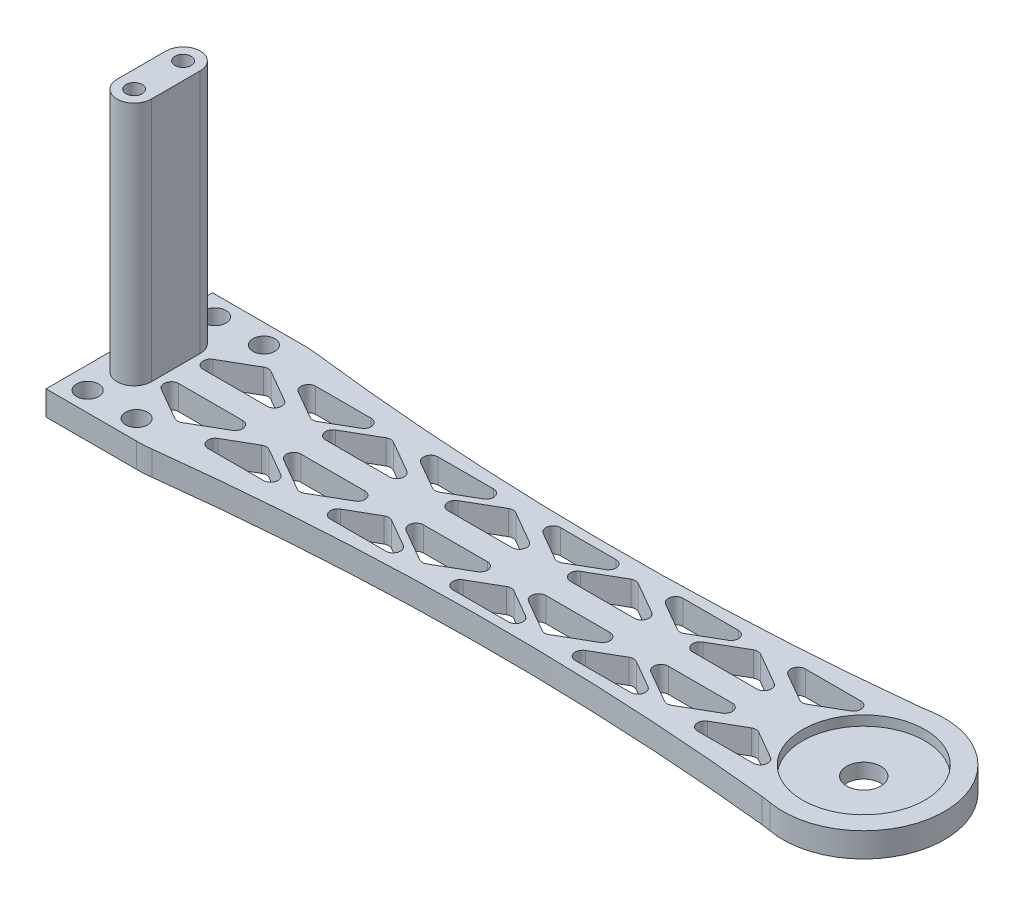
SolidWorks part; units mm, degrees
ref_plane "前视基准面" through (0, 0, 0) normal (0, 0, 1) x (1, 0, 0)
ref_plane "上视基准面" through (0, 0, 0) normal (0, 1, 0) x (1, 0, 0)
ref_plane "右视基准面" through (0, 0, 0) normal (1, 0, 0) x (0, 0, -1)
sketch "草图1" plane through (0, 0, 0) normal (0, 1, 0) x (1, 0, 0)
  line L0 (20, 17) -> (0, 17)
  line L1 (0, -28.047) -> (0, 28.047) construction
  line L2 (0, 17) -> (0, -17)
  line L3 (0, -17) -> (20, -17)
  line L5 (-45.4731, 0) -> (45.4731, 0) construction
  arc A0 (20, 17) -> (146.3579, 16.093) centre (87.1005, 562.8915) ccw
  arc A1 (146.3579, -16.093) -> (146.3579, 16.093) centre (150, 0) ccw
  arc A2 (20, -17) -> (146.3579, -16.093) centre (87.1005, -562.8915) cw
  dimension "D4" = 550
  dimension "D5" = 33
  dimension "D1" = 34
  dimension "D3" = 20
  dimension "D6" = 150
extrude "凸台-拉伸1" add sketch "草图1" along normal mid plane 5 contours A0 A1 A2 L3 L2 L0
sketch "草图2" plane through (0, 2.5, 0) normal (0, 1, 0) x (1, 0, 0)
  circle A0 centre (150, 0) radius 12.5
  dimension "D1" = 25
extrude "切除-拉伸1" cut sketch "草图2" against normal blind 2
sketch "草图3" plane through (0, 0.5, 0) normal (0, 1, 0) x (1, 0, 0)
  circle A0 centre (150, 0) radius 3.5
  dimension "D1" = 7
extrude "切除-拉伸2" cut sketch "草图3" against normal through all
sketch "草图4" plane through (0, 2.5, 0) normal (0, 1, 0) x (1, 0, 0)
  line L0 (12.5981, 2.5) -> (25.6506, 2.5)
  line L1 (26.4006, 5.299) -> (19.8744, 9.067)
  line L2 (18.3744, 9.067) -> (11.8481, 5.299)
  line L3 (-45.4731, 0) -> (45.4731, 0) construction
  line L4 (0, -28.047) -> (0, 28.047) construction
  line L5 (37.5981, 2.5) -> (50.6506, 2.5)
  line L6 (51.4006, 5.299) -> (44.8744, 9.067)
  line L7 (43.3744, 9.067) -> (36.8481, 5.299)
  line L8 (62.5981, 2.5) -> (75.6506, 2.5)
  line L9 (76.4006, 5.299) -> (69.8744, 9.067)
  line L10 (68.3744, 9.067) -> (61.8481, 5.299)
  line L11 (87.5981, 2.5) -> (100.6506, 2.5)
  line L12 (101.4006, 5.299) -> (94.8744, 9.067)
  line L13 (93.3744, 9.067) -> (86.8481, 5.299)
  line L14 (112.5981, 2.5) -> (125.6506, 2.5)
  line L15 (126.4006, 5.299) -> (119.8744, 9.067)
  line L16 (118.3744, 9.067) -> (111.8481, 5.299)
  line L17 (118.3744, -9.067) -> (111.8481, -5.299)
  line L18 (126.4006, -5.299) -> (119.8744, -9.067)
  line L19 (112.5981, -2.5) -> (125.6506, -2.5)
  line L20 (93.3744, -9.067) -> (86.8481, -5.299)
  line L21 (101.4006, -5.299) -> (94.8744, -9.067)
  line L22 (87.5981, -2.5) -> (100.6506, -2.5)
  line L23 (68.3744, -9.067) -> (61.8481, -5.299)
  line L24 (76.4006, -5.299) -> (69.8744, -9.067)
  line L25 (62.5981, -2.5) -> (75.6506, -2.5)
  line L26 (43.3744, -9.067) -> (36.8481, -5.299)
  line L27 (51.4006, -5.299) -> (44.8744, -9.067)
  line L28 (37.5981, -2.5) -> (50.6506, -2.5)
  line L29 (18.3744, -9.067) -> (11.8481, -5.299)
  line L30 (26.4006, -5.299) -> (19.8744, -9.067)
  line L31 (12.5981, -2.5) -> (25.6506, -2.5)
  arc A0 (25.6506, 2.5) -> (26.4006, 5.299) centre (25.6506, 4) ccw
  arc A1 (19.8744, 9.067) -> (18.3744, 9.067) centre (19.1244, 7.7679) ccw
  arc A2 (12.5981, 2.5) -> (11.8481, 5.299) centre (12.5981, 4) cw
  arc A3 (50.6506, 2.5) -> (51.4006, 5.299) centre (50.6506, 4) ccw
  arc A4 (44.8744, 9.067) -> (43.3744, 9.067) centre (44.1244, 7.7679) ccw
  arc A5 (37.5981, 2.5) -> (36.8481, 5.299) centre (37.5981, 4) cw
  arc A6 (75.6506, 2.5) -> (76.4006, 5.299) centre (75.6506, 4) ccw
  arc A7 (69.8744, 9.067) -> (68.3744, 9.067) centre (69.1244, 7.7679) ccw
  arc A8 (62.5981, 2.5) -> (61.8481, 5.299) centre (62.5981, 4) cw
  arc A9 (100.6506, 2.5) -> (101.4006, 5.299) centre (100.6506, 4) ccw
  arc A10 (94.8744, 9.067) -> (93.3744, 9.067) centre (94.1244, 7.7679) ccw
  arc A11 (87.5981, 2.5) -> (86.8481, 5.299) centre (87.5981, 4) cw
  arc A12 (125.6506, 2.5) -> (126.4006, 5.299) centre (125.6506, 4) ccw
  arc A13 (119.8744, 9.067) -> (118.3744, 9.067) centre (119.1244, 7.7679) ccw
  arc A14 (112.5981, 2.5) -> (111.8481, 5.299) centre (112.5981, 4) cw
  arc A15 (112.5981, -2.5) -> (111.8481, -5.299) centre (112.5981, -4) ccw
  arc A16 (119.8744, -9.067) -> (118.3744, -9.067) centre (119.1244, -7.7679) cw
  arc A17 (125.6506, -2.5) -> (126.4006, -5.299) centre (125.6506, -4) cw
  arc A18 (87.5981, -2.5) -> (86.8481, -5.299) centre (87.5981, -4) ccw
  arc A19 (94.8744, -9.067) -> (93.3744, -9.067) centre (94.1244, -7.7679) cw
  arc A20 (100.6506, -2.5) -> (101.4006, -5.299) centre (100.6506, -4) cw
  arc A21 (62.5981, -2.5) -> (61.8481, -5.299) centre (62.5981, -4) ccw
  arc A22 (69.8744, -9.067) -> (68.3744, -9.067) centre (69.1244, -7.7679) cw
  arc A23 (75.6506, -2.5) -> (76.4006, -5.299) centre (75.6506, -4) cw
  arc A24 (37.5981, -2.5) -> (36.8481, -5.299) centre (37.5981, -4) ccw
  arc A25 (44.8744, -9.067) -> (43.3744, -9.067) centre (44.1244, -7.7679) cw
  arc A26 (50.6506, -2.5) -> (51.4006, -5.299) centre (50.6506, -4) cw
  arc A27 (12.5981, -2.5) -> (11.8481, -5.299) centre (12.5981, -4) ccw
  arc A28 (19.8744, -9.067) -> (18.3744, -9.067) centre (19.1244, -7.7679) cw
  arc A29 (25.6506, -2.5) -> (26.4006, -5.299) centre (25.6506, -4) cw
  point P11 (19.1244, 9.5)
  point P14 (7, 2.5)
  point P96 (7, -2.5)
  point P97 (19.1244, -9.5)
  dimension "D6" = 1.5
  dimension "D1" = 30
  dimension "D2" = 150
  dimension "D3" = 2.5
  dimension "D4" = 7
  dimension "D5" = 7
  dimension "D7" = 5
extrude "切除-拉伸3" cut sketch "草图4" against normal through all
sketch "草图5" plane through (0, 2.5, 0) normal (0, 1, 0) x (1, 0, 0)
  line L0 (127.0814, 11) -> (138.4019, 11)
  line L1 (139.1519, 8.201) -> (133.4917, 4.933)
  line L2 (131.9917, 4.933) -> (126.3314, 8.201)
  line L3 (-45.4731, 0) -> (45.4731, 0) construction
  line L4 (102.0814, 11) -> (113.4019, 11)
  line L5 (114.1519, 8.201) -> (108.4917, 4.933)
  line L6 (106.9917, 4.933) -> (101.3314, 8.201)
  line L7 (77.0814, 11) -> (88.4019, 11)
  line L8 (89.1519, 8.201) -> (83.4917, 4.933)
  line L9 (81.9917, 4.933) -> (76.3314, 8.201)
  line L10 (52.0814, 11) -> (63.4019, 11)
  line L11 (64.1519, 8.201) -> (58.4917, 4.933)
  line L12 (56.9917, 4.933) -> (51.3314, 8.201)
  line L13 (27.0814, 11) -> (38.4019, 11)
  line L14 (39.1519, 8.201) -> (33.4917, 4.933)
  line L15 (31.9917, 4.933) -> (26.3314, 8.201)
  line L16 (31.9917, -4.933) -> (26.3314, -8.201)
  line L17 (39.1519, -8.201) -> (33.4917, -4.933)
  line L18 (27.0814, -11) -> (38.4019, -11)
  line L19 (56.9917, -4.933) -> (51.3314, -8.201)
  line L20 (64.1519, -8.201) -> (58.4917, -4.933)
  line L21 (52.0814, -11) -> (63.4019, -11)
  line L22 (81.9917, -4.933) -> (76.3314, -8.201)
  line L23 (89.1519, -8.201) -> (83.4917, -4.933)
  line L24 (77.0814, -11) -> (88.4019, -11)
  line L25 (106.9917, -4.933) -> (101.3314, -8.201)
  line L26 (114.1519, -8.201) -> (108.4917, -4.933)
  line L27 (102.0814, -11) -> (113.4019, -11)
  line L28 (131.9917, -4.933) -> (126.3314, -8.201)
  line L29 (139.1519, -8.201) -> (133.4917, -4.933)
  line L30 (127.0814, -11) -> (138.4019, -11)
  arc A0 (133.4917, 4.933) -> (131.9917, 4.933) centre (132.7417, 6.2321) cw
  arc A1 (138.4019, 11) -> (139.1519, 8.201) centre (138.4019, 9.5) cw
  arc A2 (127.0814, 11) -> (126.3314, 8.201) centre (127.0814, 9.5) ccw
  arc A3 (108.4917, 4.933) -> (106.9917, 4.933) centre (107.7417, 6.2321) cw
  arc A4 (113.4019, 11) -> (114.1519, 8.201) centre (113.4019, 9.5) cw
  arc A5 (102.0814, 11) -> (101.3314, 8.201) centre (102.0814, 9.5) ccw
  arc A6 (83.4917, 4.933) -> (81.9917, 4.933) centre (82.7417, 6.2321) cw
  arc A7 (88.4019, 11) -> (89.1519, 8.201) centre (88.4019, 9.5) cw
  arc A8 (77.0814, 11) -> (76.3314, 8.201) centre (77.0814, 9.5) ccw
  arc A9 (58.4917, 4.933) -> (56.9917, 4.933) centre (57.7417, 6.2321) cw
  arc A10 (63.4019, 11) -> (64.1519, 8.201) centre (63.4019, 9.5) cw
  arc A11 (52.0814, 11) -> (51.3314, 8.201) centre (52.0814, 9.5) ccw
  arc A12 (33.4917, 4.933) -> (31.9917, 4.933) centre (32.7417, 6.2321) cw
  arc A13 (38.4019, 11) -> (39.1519, 8.201) centre (38.4019, 9.5) cw
  arc A14 (27.0814, 11) -> (26.3314, 8.201) centre (27.0814, 9.5) ccw
  arc A15 (27.0814, -11) -> (26.3314, -8.201) centre (27.0814, -9.5) cw
  arc A16 (38.4019, -11) -> (39.1519, -8.201) centre (38.4019, -9.5) ccw
  arc A17 (33.4917, -4.933) -> (31.9917, -4.933) centre (32.7417, -6.2321) ccw
  arc A18 (52.0814, -11) -> (51.3314, -8.201) centre (52.0814, -9.5) cw
  arc A19 (63.4019, -11) -> (64.1519, -8.201) centre (63.4019, -9.5) ccw
  arc A20 (58.4917, -4.933) -> (56.9917, -4.933) centre (57.7417, -6.2321) ccw
  arc A21 (77.0814, -11) -> (76.3314, -8.201) centre (77.0814, -9.5) cw
  arc A22 (88.4019, -11) -> (89.1519, -8.201) centre (88.4019, -9.5) ccw
  arc A23 (83.4917, -4.933) -> (81.9917, -4.933) centre (82.7417, -6.2321) ccw
  arc A24 (102.0814, -11) -> (101.3314, -8.201) centre (102.0814, -9.5) cw
  arc A25 (113.4019, -11) -> (114.1519, -8.201) centre (113.4019, -9.5) ccw
  arc A26 (108.4917, -4.933) -> (106.9917, -4.933) centre (107.7417, -6.2321) ccw
  arc A27 (127.0814, -11) -> (126.3314, -8.201) centre (127.0814, -9.5) cw
  arc A28 (138.4019, -11) -> (139.1519, -8.201) centre (138.4019, -9.5) ccw
  arc A29 (133.4917, -4.933) -> (131.9917, -4.933) centre (132.7417, -6.2321) ccw
  point P5 (150, 0)
  point P9 (132.7417, 4.5)
  point P12 (144, 11)
  point P96 (144, -11)
  point P97 (132.7417, -4.5)
  dimension "D6" = 1.5
  dimension "D1" = 6.5
  dimension "D2" = 11
  dimension "D3" = 6
  dimension "D4" = 30
  dimension "D5" = 30
  dimension "D7" = 5
extrude "切除-拉伸4" cut sketch "草图5" against normal through all
sketch "草图6" plane through (0, 2.5, 0) normal (0, 1, 0) x (1, 0, 0)
  line L0 (0, -28.047) -> (0, 28.047) construction
  line L1 (-45.4731, 0) -> (45.4731, 0) construction
  circle A0 centre (4.5, 13) radius 2.25
  circle A1 centre (14.5, 13) radius 2.25
  dimension "D1" = 4.5
  dimension "D4" = 4.5
  dimension "D2" = 10
  dimension "D3" = 4.5
  dimension "D5" = 13
extrude "切除-拉伸5" cut sketch "草图6" against normal through all
mirror "镜向1" about plane through (0, 0, 0) normal (0, 0, 1) of "切除-拉伸5"
fillet "圆角1" radius 25 4 edges at (20, 0, 17) (146.3579, 0, 16.093) (146.3579, 0, -16.093) (20, 0, -17)
sketch "草图8" plane through (0, 2.5, 0) normal (0, 1, 0) x (1, 0, 0)
  line L0 (6, 5) -> (6, -5) construction
  line L1 (9.5, 5) -> (9.5, -5)
  line L2 (2.5, 5) -> (2.5, -5)
  line L3 (-45.4731, 0) -> (45.4731, 0) construction
  line L4 (0, -28.047) -> (0, 28.047) construction
  arc A0 (9.5, 5) -> (2.5, 5) centre (6, 5) ccw
  arc A1 (2.5, -5) -> (9.5, -5) centre (6, -5) ccw
  point P2 (6, 0)
  point P10 (6, 8.5)
  dimension "D1" = 8.5
  dimension "D2" = 7
  dimension "D3" = 6
extrude "凸台-拉伸2" add sketch "草图8" along normal blind 50
sketch "草图9" plane through (0, 52.5, 0) normal (0, 1, 0) x (1, 0, 0)
  arc A0 (2.5, -5) -> (9.5, -5) centre (6, -5) ccw construction
  arc A1 (9.5, 5) -> (2.5, 5) centre (6, 5) ccw construction
  point P0 (6, 5)
  point P1 (6, -5)
hole_wizard "M4 螺纹孔1" positions "3D草图2" profile "草图10" tap size "M4" standard "ISO"
sketch3d "3D草图2"
  point P0 (6, 52.5, -5)
  point P3 (6, 52.5, 5)
sketch "草图10" plane through (6, 52.5, -5) normal (1, 0, 0) x (0, 0, 1)
  line L0 (0, 0) -> (0, 12.4914)
  line L1 (0, 12.4914) -> (1.65, 11.5)
  line L2 (1.65, 11.5) -> (1.65, 0)
  line L5 (1.65, 0) -> (0, 0)
  line L10 (0, 12.4914) -> (-1.65, 11.5) construction
  line L11 (0, -6.35) -> (0, 107.95) construction
  dimension "螺纹孔钻头直径" = 3.3
  dimension "螺纹孔钻头深度" = 11.5
  dimension "导头角度" = 118
cosmetic thread "孔螺蚊线1" parameters "D1"=8, "D2"=4
cosmetic thread "孔螺蚊线2" parameters "D1"=8, "D2"=4
